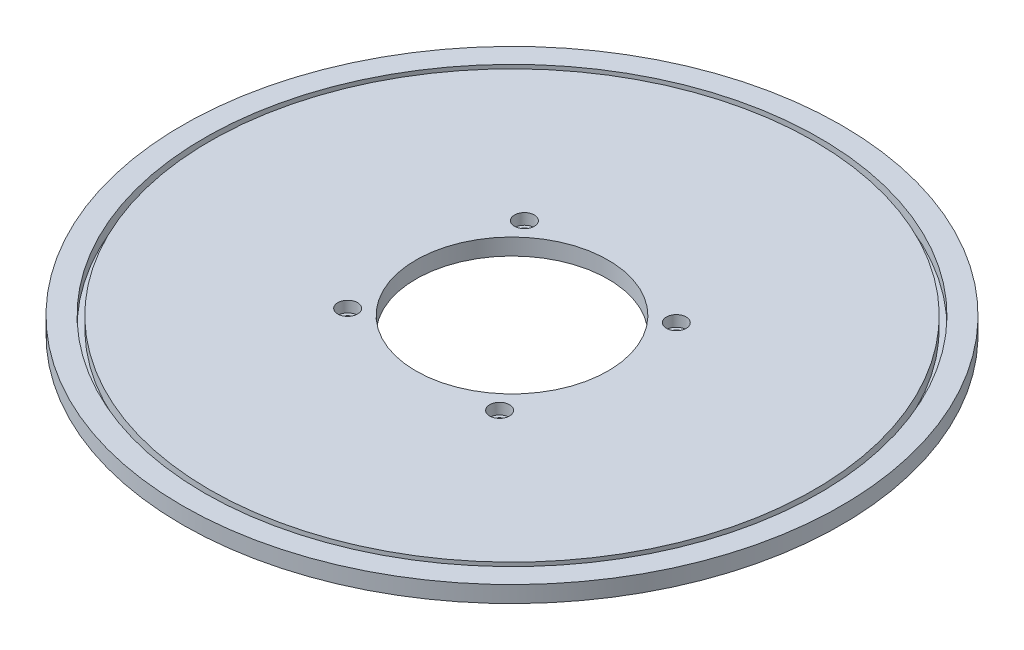
SolidWorks part; units mm, degrees
ref_plane "Front Plane" through (0, 0, 0) normal (0, 0, 1) x (1, 0, 0)
ref_plane "Top Plane" through (0, 0, 0) normal (0, 1, 0) x (1, 0, 0)
ref_plane "Right Plane" through (0, 0, 0) normal (1, 0, 0) x (0, 0, -1)
sketch "Sketch1" plane through (0, 0, 0) normal (0, 1, 0) x (1, 0, 0)
  circle A0 centre (0, 0) radius 300
  point P0 (0, 0)
  dimension "D1" = 600
extrude "plate" add sketch "Sketch1" along normal blind 15
sketch "Sketch2" plane through (0, 15, 0) normal (0, 1, 0) x (1, 0, 0)
  circle A0 centre (0, 0) radius 87.5
  dimension "D1" = 175
extrude "bearing-hole" cut sketch "Sketch2" against normal through all
sketch "Sketch4" plane through (0, 15, 0) normal (0, 1, 0) x (1, 0, 0)
  circle A0 centre (0, 0) radius 280
  circle A1 centre (0, 0) radius 275
  point P0 (0, 0)
  point P6 (0, 0)
  dimension "D1" = 560
  dimension "D2" = 550
extrude "Cut-Extrude3" cut sketch "Sketch4" against normal blind 10
hole_wizard "CBORE for M10 SHCS" positions "Sketch5" profile "Sketch6" counterbore size "M10" standard "ANSI Metric" end condition through all
sketch "Sketch5" plane through (0, 15, 0) normal (0, 1, 0) x (0.9972, 0, 0.0753)
  line L1 (75, -75) -> (-75, -75) construction
  line L2 (75, -75) -> (75, 75) construction
  line L3 (75, 75) -> (-75, 75) construction
  line L4 (-75, -75) -> (-75, 75) construction
  line L5 (75, -75) -> (-75, 75) construction
  line L6 (75, 75) -> (-75, -75) construction
  point P36 (0, 0)
  point P198 (-75, 75)
  point P201 (75, 75)
  point P204 (75, -75)
  point P207 (-75, -75)
sketch "Sketch6" plane through (0, 15, 0) normal (1, 0, 0) x (0, 0, 1)
  line L0 (0, 0) -> (0, 15)
  line L1 (0, 15) -> (6, 15)
  line L2 (6, 15) -> (6, 10)
  line L3 (6, 10) -> (9, 10)
  line L4 (9, 10) -> (9, 0)
  line L5 (9, 0) -> (0, 0)
  line L6 (0, -6.35) -> (0, 107.95) construction
  dimension "Thru Hole Dia." = 12
  dimension "Thru Hole Depth" = 15
  dimension "C'Bore Dia." = 18
  dimension "C'Bore Depth" = 10
